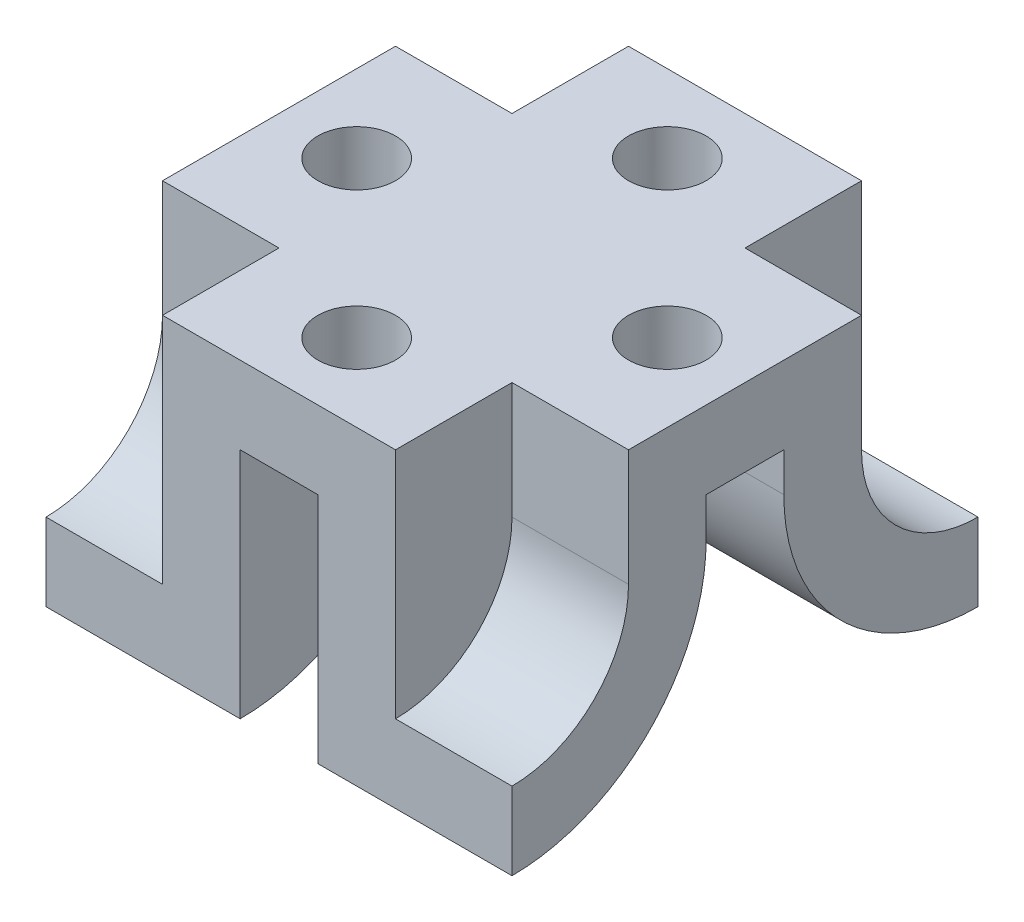
SolidWorks part; units mm, degrees
ref_plane "前视基准面" through (0, 0, 0) normal (0, 0, 1) x (1, 0, 0)
ref_plane "上视基准面" through (0, 0, 0) normal (0, 1, 0) x (1, 0, 0)
ref_plane "右视基准面" through (0, 0, 0) normal (1, 0, 0) x (0, 0, -1)
other "Configuration Table"
ref_plane "基准面3" through (0, 0, 0) normal (0, 0, 1) x (1, 0, 0)
sketch "草图2" plane through (0, 0, 0) normal (0, 0, 1) x (1, 0, 0)
  line L0 (0, 19.6794) -> (0, 16) construction
  line L1 (2, 0) -> (12, 0)
  line L2 (12, 0) -> (12, 4)
  line L3 (12, 4) -> (6, 4)
  line L4 (6, 4) -> (6, 16)
  line L5 (6, 16) -> (-6, 16)
  line L7 (-2, 12) -> (2, 12)
  line L8 (2, 12) -> (2, 0)
  line L9 (-2, 12) -> (-2, 0)
  line L10 (-6, 4) -> (-6, 16)
  line L11 (-12, 4) -> (-6, 4)
  line L12 (-12, 0) -> (-12, 4)
  line L13 (-2, 0) -> (-12, 0)
  line L14 (0, 12) -> (0, -11.6794) construction
  line L15 (-2, 0) -> (2, 0)
  dimension "D1" = 4
  dimension "D2" = 10
  dimension "D3" = 16
  dimension "D4" = 4
  dimension "D5" = 2
  dimension "D6" = 4
extrude "凸台-拉伸1" add sketch "草图2" against normal mid plane 24 contours L13 L9 L7 L8 L1 L2 L3 L4 L5 L10 L11 L12 region at (2.2884, 6, 0)
ref_plane "基准面4" through (12, 0, 0) normal (1, 0, 0) x (0, 0, -1)
sketch "草图7" plane through (12, 0, 0) normal (1, 0, 0) x (0, 0, -1)
  line L0 (0, 18.3666) -> (0, -1.6675) construction
  line L1 (-12, 4) -> (-12, 16) construction
  line L2 (-2, 10) -> (-2, 12)
  line L3 (12, 16) -> (-12, 16) construction
  line L4 (-6, 10) -> (-6, 16)
  line L5 (-6, 16) -> (6, 16)
  line L6 (-2, 12) -> (2, 12)
  line L7 (-2, 10) -> (-2, 16) construction
  line L8 (-12, 0) -> (-12, 4)
  line L9 (-12, 0) -> (12, 0)
  line L10 (12, 0) -> (12, 4)
  line L11 (6, 10) -> (6, 16)
  line L12 (2, 10) -> (2, 12)
  arc A0 (-12, 0) -> (-2, 10) centre (-12, 10) ccw
  arc A1 (-12, 4) -> (-6, 10) centre (-12, 10) ccw
  arc A2 (12, 4) -> (6, 10) centre (12, 10) cw
  arc A3 (12, 0) -> (2, 10) centre (12, 10) cw
  point P26 (0, 0)
  point P27 (0, 12)
  point P28 (0, 16)
  dimension "D1" = 10
  dimension "D3" = 4
  dimension "D2" = 4
extrude "切除-拉伸5" cut sketch "草图7" against normal blind 24 contours L9 A3 L12 L6 L2 A0 region at (12, 4.2221, 0)
extrude "凸台-拉伸5" add sketch "草图7<4>" against normal blind 24 contours A3 L10 A2 L11 L5 L4 A1 L8 A0 L2 L6 L12 region at (12, 3.1329, 5.1329)
sketch "草图7<4>" plane through (12, 0, 0) normal (1, 0, 0) x (0, 0, -1) same geometry as "草图7"
extrude "切除-拉伸6" cut sketch "草图2<4>" against normal mid plane 24 contours L9 L15 L8 L7 region at (0, 6, 0)
sketch "草图2<4>" plane through (0, 0, 0) normal (0, 0, 1) x (1, 0, 0) same geometry as "草图2"
sketch "草图9" plane through (0, 16, 0) normal (0, 1, 0) x (1, 0, 0)
  line L0 (0, 18.307) -> (0, -20.738) construction
  line L1 (6, 12) -> (-6, 12) construction
  line L2 (-18.5501, 0) -> (15.7826, 0) construction
  line L3 (-12, -6) -> (-12, 6) construction
  circle A0 centre (0, 8) radius 2
  circle A1 centre (-8, 0) radius 2
  circle A2 centre (8, 0) radius 2
  circle A3 centre (0, -8) radius 2
  dimension "D2" = 4
  dimension "D3" = 4
  dimension "D1" = 4
  dimension "D4" = 4
extrude "切除-拉伸7" cut sketch "草图9" against normal blind 4
